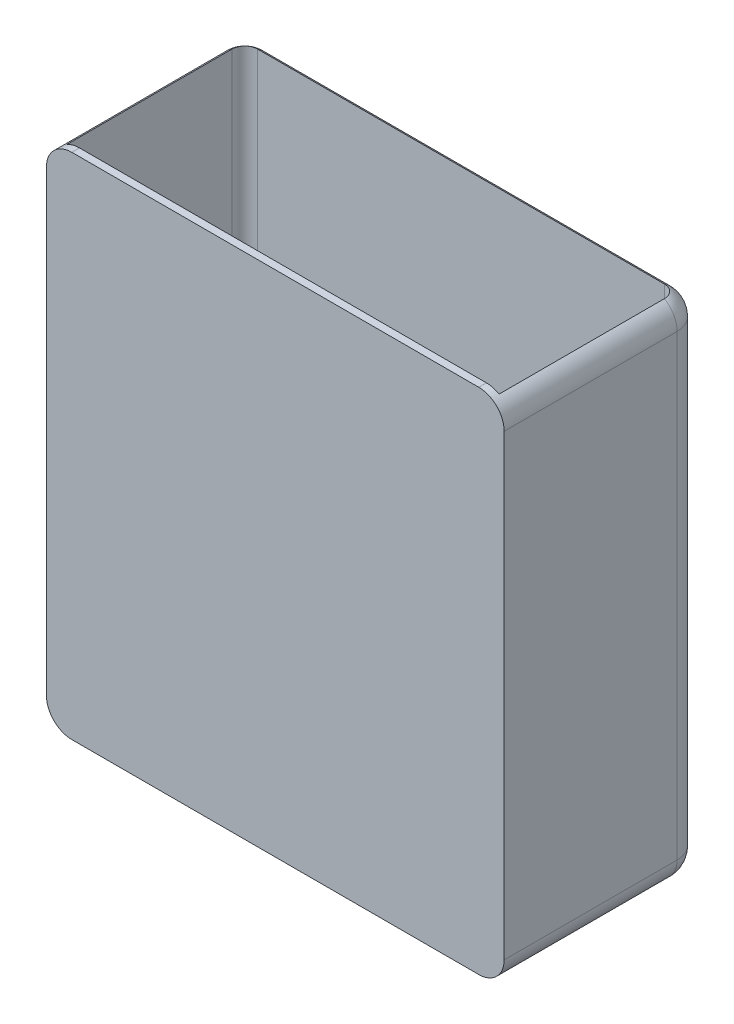
SolidWorks part; units mm, degrees
ref_plane "Front Plane" through (0, 0, 0) normal (0, 0, 1) x (1, 0, 0)
ref_plane "Top Plane" through (0, 0, 0) normal (0, 1, 0) x (1, 0, 0)
ref_plane "Right Plane" through (0, 0, 0) normal (1, 0, 0) x (0, 0, -1)
sketch "Sketch1" plane through (0, 0, 0) normal (0, 1, 0) x (1, 0, 0)
  line L1 (-80, 45) -> (80, 45)
  line L2 (-90, 35) -> (-90, -35)
  line L3 (-90, -35) -> (90, -35)
  line L4 (90, 35) -> (90, -35)
  line L5 (0, -35) -> (0, 45) construction
  line L6 (-90, 0) -> (90, 0) construction
  arc A0 (90, 35) -> (80, 45) centre (80, 35) ccw
  arc A1 (-80, 45) -> (-90, 35) centre (-80, 35) ccw
  point P0 (0, 0)
  point P6 (90, 45)
  point P10 (-90, 45)
  dimension "D3" = 10
  dimension "D1" = 180
  dimension "D2" = 80
extrude "Boss-Extrude1" add sketch "Sketch1" against normal blind 200
sketch "Sketch2" plane through (0, 0, 0) normal (0, 1, 0) x (1, 0, 0)
  line L8 (85, -30) -> (85, 35)
  line L9 (80, 40) -> (-80, 40)
  line L10 (-85, 35) -> (-85, -30)
  line L11 (-85, -30) -> (85, -30)
  line L12 (85, -30) -> (85, 35)
  line L13 (80, 40) -> (-80, 40)
  line L14 (-85, 35) -> (-85, -30)
  line L15 (-85, -30) -> (85, -30)
  arc A4 (85, 35) -> (80, 40) centre (80, 35) ccw
  arc A5 (-80, 40) -> (-85, 35) centre (-80, 35) ccw
  arc A6 (85, 35) -> (80, 40) centre (80, 35) ccw
  arc A7 (-80, 40) -> (-85, 35) centre (-80, 35) ccw
  dimension "D1" = 5
extrude "Cut-Extrude1" cut sketch "Sketch2" against normal blind 193
fillet "Fillet1" radius 10 5 edges at (90, -200, 0) (87.0711, -200, -42.0711) (-90, -200, 0) (-87.0711, -200, -42.0711) (0, -200, -45)
fillet "Fillet2" radius 10 2 edges at (90, 0, 0) (-90, 0, 0)
sketch "Sketch5" plane through (0, 0, 35) normal (0, 0, 1) x (1, 0, 0)
  line L1 (-99.571, 11.8368) -> (122.406, 11.8368)
  line L2 (-99.571, 11.8368) -> (-99.571, -210.6713)
  line L3 (-99.571, -210.6713) -> (122.406, -210.6713)
  line L4 (122.406, 11.8368) -> (122.406, -210.6713)
  line L5 (-99.571, 11.8368) -> (122.406, -210.6713) construction
  line L6 (-99.571, -210.6713) -> (122.406, 11.8368) construction
  point P4 (11.4175, -99.4173)
extrude "Cut-Extrude2" cut sketch "Sketch5" against normal blind 2
